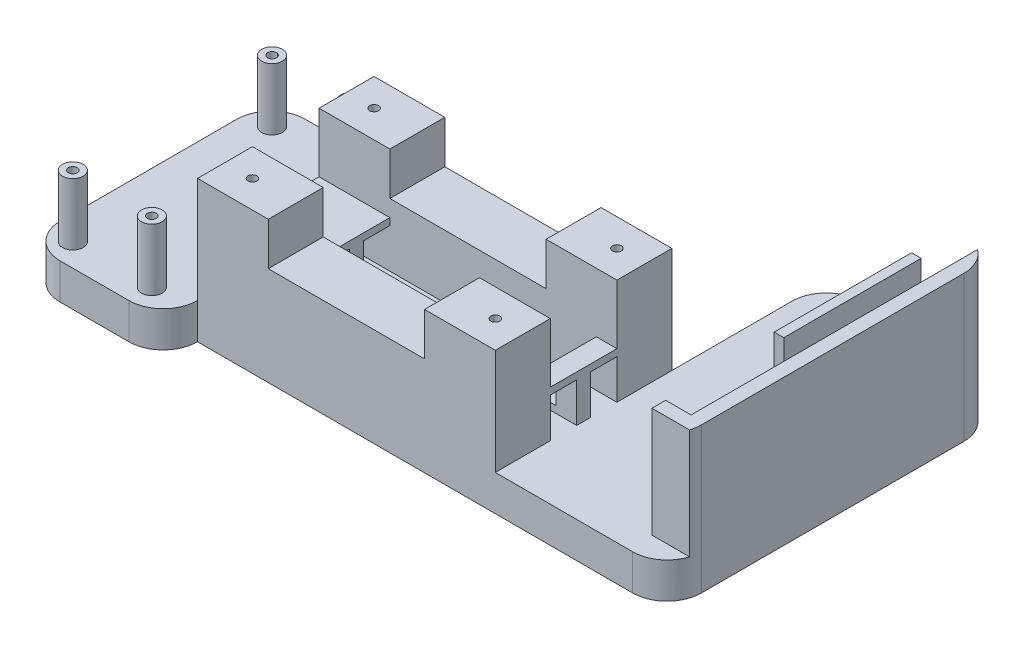
SolidWorks part; units mm, degrees
ref_plane "前视基准面" through (0, 0, 0) normal (0, 0, 1) x (1, 0, 0)
ref_plane "上视基准面" through (0, 0, 0) normal (0, 1, 0) x (1, 0, 0)
ref_plane "右视基准面" through (0, 0, 0) normal (1, 0, 0) x (0, 0, -1)
sketch "草图1" plane through (0, 0, 0) normal (0, 0, 1) x (1, 0, 0)
  line L1 (-42.1231, 25.5984) -> (44.5769, 25.5984)
  line L2 (-42.1231, 25.5984) -> (-42.1231, 5.5984)
  line L3 (-42.1231, 5.5984) -> (44.5769, 5.5984)
  line L4 (44.5769, 25.5984) -> (44.5769, 5.5984)
  line L5 (-21.5231, 25.5984) -> (23.9769, 25.5984)
  line L6 (-21.5231, 25.5984) -> (-21.5231, 13.1284)
  line L7 (-21.5231, 13.1284) -> (23.9769, 13.1284)
  line L8 (23.9769, 25.5984) -> (23.9769, 13.1284)
  dimension "D1" = 86.7
  dimension "D2" = 20
  dimension "D3" = 45.5
  dimension "D4" = 20.6
  dimension "D5" = 20.6
  dimension "D6" = 12.47
extrude "凸台-拉伸1" add sketch "草图1" along normal blind 16 contours L1 L8 L7 L6 L2 L3 L4 region at (-31.8231, 24.7086, 0)
sketch "草图2" plane through (0, 25.5984, 0) normal (0, 1, 0) x (1, 0, 0)
  line L0 (23.9769, -8) -> (28.5769, -8) construction
  line L1 (23.9769, -16) -> (23.9769, 0) construction
  line L2 (28.5769, -8) -> (28.5769, 0) construction
  line L3 (23.9769, 0) -> (44.5769, 0) construction
  line L4 (28.5769, 0) -> (28.5769, -16) construction
  line L5 (23.9769, -16) -> (44.5769, -16) construction
  line L7 (28.5769, 0) -> (44.5769, -16) construction
  line L8 (44.5769, 0) -> (28.5769, -16) construction
  point P16 (36.5769, -8)
  dimension "D1" = 4.6
hole_wizard "Ø1.0mm 暗销孔1" positions "草图2" profile "草图3" hole size "Ø1.0" standard "GB" end condition through all
sketch "草图3" plane through (36.5769, 25.5984, 8) normal (1, 0, 0) x (0, 0, 1)
  line L0 (0, 0) -> (0, 20)
  line L1 (0, 20) -> (1.3, 20)
  line L2 (1.3, 20) -> (1.3, 0)
  line L5 (1.3, 0) -> (0, 0)
  line L11 (0, -6.35) -> (0, 107.95) construction
  dimension "通孔孔直径" = 2.6
  dimension "通孔孔深度" = 20
sketch "草图4" plane through (0, 25.5984, 0) normal (0, 1, 0) x (1, 0, 0)
  line L0 (-21.5231, -8) -> (-26.1231, -8) construction
  line L1 (-21.5231, -16) -> (-21.5231, 0) construction
  line L2 (-26.1231, -8) -> (-26.1231, 0) construction
  line L3 (-42.1231, 0) -> (-21.5231, 0) construction
  line L4 (-26.1231, 0) -> (-26.1231, -16) construction
  line L5 (-42.1231, -16) -> (-21.5231, -16) construction
  line L6 (-42.1231, 0) -> (-26.1231, -16) construction
  line L7 (-26.1231, -16) -> (-26.1231, 0) construction
  line L8 (-26.1231, 0) -> (-42.1231, -16) construction
  point P15 (-34.1231, -8)
  dimension "D1" = 4.6
hole_wizard "Ø1.0mm 暗销孔2" positions "草图4" profile "草图5" hole size "Ø1.0" standard "GB" end condition through all
sketch "草图5" plane through (-34.1231, 25.5984, 8) normal (1, 0, 0) x (0, 0, 1)
  line L0 (0, 0) -> (0, 20)
  line L1 (0, 20) -> (1.3, 20)
  line L2 (1.3, 20) -> (1.3, 0)
  line L5 (1.3, 0) -> (0, 0)
  line L11 (0, -6.35) -> (0, 107.95) construction
  dimension "通孔孔直径" = 2.6
  dimension "通孔孔深度" = 20
sketch "草图7" plane through (0, 25.5984, 0) normal (0, 1, 0) x (1, 0, 0)
sketch "草图8" plane through (0, 5.5984, 0) normal (0, -1, 0) x (1, 0, 0)
  line L1 (-42.1231, 16) -> (44.5769, 16)
  line L2 (-42.1231, 16) -> (-42.1231, 0)
  line L3 (-42.1231, 0) -> (44.5769, 0)
  line L4 (44.5769, 16) -> (44.5769, 0)
extrude "凸台-拉伸2" add sketch "草图8" along normal blind 21.2
sketch "草图9" plane through (0, 0, 0) normal (0, 0, -1) x (-1, 0, 0)
  line L0 (42.1231, 25.5984) -> (42.1231, -15.6016) construction
  line L1 (-44.5769, -15.6016) -> (42.1231, -15.6016)
  line L2 (-44.5769, -15.6016) -> (-44.5769, -5.2016)
  line L3 (-44.5769, -5.2016) -> (42.1231, -5.2016)
  line L4 (42.1231, -15.6016) -> (42.1231, -5.2016)
  dimension "D1" = 10.4
extrude "凸台-拉伸3" add sketch "草图9" along normal blind 9.7
sketch "草图15" plane through (0, -5.2016, 0) normal (0, 1, 0) x (1, 0, 0)
  line L5 (-42.1231, 9.7) -> (-21.5231, 9.7)
  line L6 (-42.1231, 9.7) -> (-42.1231, 7.7)
  line L7 (-42.1231, 7.7) -> (-21.5231, 7.7)
  line L8 (-21.5231, 9.7) -> (-21.5231, 7.7)
  dimension "D1" = 2
extrude "凸台-拉伸8" add sketch "草图15" along normal blind 13.5
sketch "草图16" plane through (0, 0, -9.7) normal (0, 0, -1) x (-1, 0, 0)
  line L0 (42.1231, -15.6016) -> (42.1231, 8.2984) construction
  line L1 (21.5231, 8.2984) -> (42.1231, 8.2984)
  line L2 (21.5231, 8.2984) -> (21.5231, 6.2984)
  line L3 (21.5231, 6.2984) -> (42.1231, 6.2984)
  line L4 (42.1231, 8.2984) -> (42.1231, 6.2984)
  dimension "D1" = 2
extrude "凸台-拉伸9" add sketch "草图16" against normal blind 10.5
mirror "镜向20" about plane through (0, 0, -9.7) normal (0, 0, 1) of "Ø1.0mm 暗销孔2", "Ø1.0mm 暗销孔1", "凸台-拉伸3", "凸台-拉伸1", "凸台-拉伸2", "凸台-拉伸8", "凸台-拉伸9"
sketch "草图19" plane through (44.5769, 0, 0) normal (1, 0, 0) x (0, 0, -1)
  line L0 (35.4, 25.5984) -> (35.4, -15.6016) construction
  line L1 (-16, -15.6016) -> (35.4, -15.6016)
  line L2 (-16, -15.6016) -> (-16, -5.2016)
  line L3 (-16, -5.2016) -> (35.4, -5.2016)
  line L4 (35.4, -15.6016) -> (35.4, -5.2016)
  line L5 (19.4, -5.2016) -> (0, -5.2016) construction
  dimension "D1" = 0
  dimension "D2" = 10.4
extrude "凸台-拉伸10" add sketch "草图19" along normal blind 50
sketch "草图25" plane through (0, 0, -35.4) normal (0, 0, -1) x (-1, 0, 0)
  line L0 (-94.5769, -15.6016) -> (42.1231, -15.6016) construction
  line L1 (-94.5769, -5.2016) -> (-44.5769, -5.2016)
  line L2 (-94.5769, -5.2016) -> (-94.5769, -15.6016)
  line L3 (-94.5769, -15.6016) -> (-44.5769, -15.6016)
  line L4 (-44.5769, -5.2016) -> (-44.5769, -15.6016)
extrude "凸台-拉伸11" add sketch "草图25" along normal blind 45
sketch "草图26" plane through (0, -5.2016, 0) normal (0, 1, 0) x (1, 0, 0)
  line L0 (44.5769, 0) -> (94.5769, 0) construction
  line L1 (94.5769, 80.4) -> (94.5769, -16) construction
  line L2 (44.5769, 80.4) -> (94.5769, 80.4) construction
  line L7 (83.1769, -9) -> (94.5769, -9)
  line L8 (83.1769, -9) -> (83.1769, -5)
  line L9 (83.1769, -5) -> (90.5769, -5)
  line L10 (94.5769, -9) -> (94.5769, -5)
  line L12 (94.5769, -5) -> (94.5769, 80.4)
  line L13 (94.5769, 80.4) -> (90.5769, 80.4)
  line L14 (90.5769, -5) -> (90.5769, 80.4)
  line L15 (83.1769, -5) -> (83.1769, 28) construction
  line L29 (83.1769, 28) -> (84.5769, 28)
  line L31 (83.1769, 68) -> (84.5769, 68)
  line L32 (84.5769, 28) -> (84.5769, 68)
  line L36 (83.1769, 68) -> (83.1769, 83.3786) construction
  line L37 (83.1769, 28) -> (81.7769, 28)
  line L39 (83.1769, 68) -> (81.7769, 68)
  line L40 (81.7769, 28) -> (81.7769, 68)
  dimension "D1" = 4
  dimension "D2" = 5
  dimension "D3" = 4
  dimension "D4" = 7.4
  dimension "D5" = 1.4
  dimension "D6" = 28
  dimension "D7" = 1.4
  dimension "D8" = 40
  dimension "D9" = 6
extrude "凸台-拉伸12" add sketch "草图26" along normal blind 32
sketch "草图28" plane through (0, -5.2016, 0) normal (0, 1, 0) x (1, 0, 0)
  line L0 (84.5769, 28) -> (84.5769, 68) construction
  line L13 (90.5769, -5) -> (84.5769, -5)
  line L14 (90.5769, -5) -> (90.5769, 80.4)
  line L15 (90.5769, 80.4) -> (84.5769, 80.4)
  line L16 (84.5769, 28) -> (84.5769, 80.4)
  line L17 (94.5769, 80.4) -> (90.5769, 80.4) construction
  line L19 (84.5769, -5) -> (82.5769, -5)
  line L21 (84.5769, 28) -> (82.5769, 28)
  line L22 (82.5769, -5) -> (82.5769, 28)
  dimension "D1" = 6
  dimension "D2" = 0
  dimension "D3" = 2
  dimension "D4" = 33
extrude "切除-拉伸1" cut sketch "草图28" against normal blind 5
sketch "草图29" plane through (-42.1231, 0, 0) normal (-1, 0, 0) x (0, 0, 1)
  line L0 (-35.4, 25.5984) -> (-35.4, -15.6016) construction
  line L1 (-35.4, -5.1986) -> (16, -5.1986)
  line L2 (-35.4, -5.1986) -> (-35.4, -15.6016)
  line L3 (-35.4, -15.6016) -> (16, -15.6016)
  line L4 (16, -5.1986) -> (16, -15.6016)
extrude "凸台-拉伸13" add sketch "草图29" along normal blind 40
sketch "草图32" plane through (0, 0, -35.4) normal (0, 0, -1) x (-1, 0, 0)
  line L1 (42.1231, -5.1986) -> (82.1231, -5.1986)
  line L2 (42.1231, -5.1986) -> (42.1231, -15.6016)
  line L3 (42.1231, -15.6016) -> (82.1231, -15.6016)
  line L4 (82.1231, -5.1986) -> (82.1231, -15.6016)
extrude "凸台-拉伸14" add sketch "草图32" along normal blind 10
sketch "草图33" plane through (0, 0, 16) normal (0, 0, 1) x (1, 0, 0)
  line L0 (94.5769, -15.6016) -> (-82.1231, -15.6016) construction
  line L1 (-82.1231, -5.1986) -> (-42.1231, -5.1986)
  line L2 (-82.1231, -5.1986) -> (-82.1231, -15.6016)
  line L3 (-82.1231, -15.6016) -> (-42.1231, -15.6016)
  line L4 (-42.1231, -5.1986) -> (-42.1231, -15.6016)
extrude "凸台-拉伸15" add sketch "草图33" along normal blind 10
sketch "草图34" plane through (0, -5.1986, 0) normal (0, 1, 0) x (1, 0, 0)
  line L0 (-42.1231, 9.7) -> (-82.1231, 9.7) construction
  line L1 (-55.1231, 38.7) -> (-72.1231, 38.7)
  line L2 (-52.1231, 35.7) -> (-52.1231, -16.3)
  line L3 (-55.1231, -19.3) -> (-72.1231, -19.3)
  line L4 (-75.1231, 35.7) -> (-75.1231, -16.3)
  line L5 (-42.1231, 7.7) -> (-42.1231, 11.7) construction
  line L6 (-82.1231, -26) -> (-82.1231, 45.4) construction
  line L7 (-42.1231, 11.7) -> (-42.1231, 19.4) construction
  circle A0 centre (-52.1231, 38.7) radius 3
  circle A1 centre (-52.1231, -19.3) radius 3
  circle A2 centre (-75.1231, 38.7) radius 3
  circle A3 centre (-75.1231, -19.3) radius 3
  dimension "D4" = 6
  dimension "D5" = 6
  dimension "D7" = 6
  dimension "D8" = 6
  dimension "D1" = 23
  dimension "D2" = 58
  dimension "D3" = 29
  dimension "D6" = 10
extrude "凸台-拉伸16" add sketch "草图34" along normal blind 18 contours A0 | A2 | A1 | A3 region at (-52.1231, -5.1986, -38.7) region at (-75.1231, -5.1986, -38.7) region at (-52.1231, -5.1986, 19.3) region at (-75.1231, -5.1986, 19.3)
sketch "草图35" plane through (0, 12.8014, 0) normal (0, 1, 0) x (1, 0, 0)
  point P0 (-52.1231, 38.7)
hole_wizard "Ø1.0mm 暗销孔3" positions "草图35" profile "草图36" hole size "Ø1.0" standard "GB" end condition through all
sketch "草图36" plane through (-52.1231, 12.8014, -38.7) normal (1, 0, 0) x (0, 0, 1)
  line L0 (0, 0) -> (0, 28.403)
  line L1 (0, 28.403) -> (1.3, 28.403)
  line L2 (1.3, 28.403) -> (1.3, 0)
  line L5 (1.3, 0) -> (0, 0)
  line L11 (0, -6.35) -> (0, 107.95) construction
  dimension "通孔孔直径" = 2.6
  dimension "通孔孔深度" = 28.403
sketch "草图37" plane through (0, 12.8014, 0) normal (0, 1, 0) x (1, 0, 0)
  line L0 (-75.1231, 41.7) -> (-75.1231, 35.7) construction
  line L1 (-75.1231, 35.7) -> (-72.1231, 38.7) construction
  line L2 (-72.1231, 38.7) -> (-78.1231, 38.7) construction
  line L3 (-75.1231, -16.3) -> (-75.1231, -22.3) construction
  line L4 (-75.1231, -22.3) -> (-72.1231, -19.3) construction
  line L5 (-72.1231, -19.3) -> (-78.1231, -19.3) construction
  line L6 (-52.1231, -16.3) -> (-52.1231, -22.3) construction
  line L7 (-52.1231, -22.3) -> (-49.1231, -19.3) construction
  line L8 (-49.1231, -19.3) -> (-55.1231, -19.3) construction
  circle A0 centre (-75.1231, 38.7) radius 3 construction
  circle A1 centre (-75.1231, 38.7) radius 3 construction
  circle A2 centre (-75.1231, -19.3) radius 3 construction
  circle A3 centre (-75.1231, -19.3) radius 3 construction
  circle A4 centre (-52.1231, -19.3) radius 3 construction
  circle A5 centre (-52.1231, -19.3) radius 3 construction
  point P29 (-75.1231, 38.7)
  point P31 (-75.1231, -19.3)
  point P33 (-52.1231, -19.3)
hole_wizard "Ø1.0mm 暗销孔4" positions "草图37" profile "草图38" hole size "Ø1.0" standard "GB" end condition through all
sketch "草图38" plane through (-52.1231, 12.8014, 19.3) normal (1, 0, 0) x (0, 0, 1)
  line L0 (0, 0) -> (0, 28.403)
  line L1 (0, 28.403) -> (1.3, 28.403)
  line L2 (1.3, 28.403) -> (1.3, 0)
  line L5 (1.3, 0) -> (0, 0)
  line L11 (0, -6.35) -> (0, 107.95) construction
  dimension "通孔孔直径" = 2.6
  dimension "通孔孔深度" = 28.403
sketch "草图39" plane through (0, -5.1986, 0) normal (0, 1, 0) x (1, 0, 0)
  line L0 (-75.1231, 38.7) -> (-52.1231, 38.7) construction
  line L1 (-52.1231, 38.7) -> (-52.1231, -19.3) construction
fillet "圆角1" radius 10 6 edges at (44.5769, -10.4016, -80.4) (94.5769, -10.4016, 16) (-42.1231, -10.4001, -45.4) (-42.1231, -10.4001, 26) (-82.1231, -10.4001, -45.4) (-82.1231, -10.4001, 26)
fillet "圆角2" radius 10 1 edges at (94.5769, 5.5984, -80.4)
sketch "草图40" plane through (0, -5.2016, 0) normal (0, 1, 0) x (1, 0, 0)
  line L0 (23.9769, 19.4) -> (23.9769, 0) construction
  line L1 (44.5769, 19.4) -> (44.5769, 0) construction
  line L2 (23.9769, 9.7) -> (44.5769, 9.7) construction
  line L4 (38.5769, 11.7) -> (44.5769, 11.7)
  line L5 (38.5769, 11.7) -> (38.5769, 7.7)
  line L6 (38.5769, 7.7) -> (44.5769, 7.7)
  line L7 (44.5769, 11.7) -> (44.5769, 7.7)
  dimension "D1" = 6
  dimension "D2" = 4
  dimension "D3" = 2
extrude "凸台-拉伸17" add sketch "草图40" along normal blind 11.5
sketch "草图42" plane through (0, 6.2984, 0) normal (0, 1, 0) x (1, 0, 0)
  line L0 (38.5769, 9.7) -> (44.5769, 9.7) construction
  line L1 (38.5769, 11.7) -> (38.5769, 7.7) construction
  line L2 (44.5769, 7.7) -> (44.5769, 11.7) construction
  line L3 (41.5769, 11.7) -> (41.5769, 7.7) construction
  line L4 (44.5769, 11.7) -> (38.5769, 11.7) construction
  line L5 (38.5769, 7.7) -> (44.5769, 7.7) construction
  line L7 (38.5769, 0) -> (44.5769, 0)
  line L8 (38.5769, 0) -> (38.5769, 19.4)
  line L9 (38.5769, 19.4) -> (44.5769, 19.4)
  line L10 (44.5769, 0) -> (44.5769, 19.4)
  line L11 (38.5769, 0) -> (44.5769, 19.4) construction
  line L12 (38.5769, 19.4) -> (44.5769, 0) construction
  point P12 (41.5769, 9.7)
  dimension "D1" = 19.4
extrude "凸台-拉伸18" add sketch "草图42" along normal blind 2
sketch "草图44" plane through (0, -5.2016, 0) normal (0, 1, 0) x (1, 0, 0)
  line L0 (-21.5231, 11.7) -> (38.5769, 11.7) construction
  line L1 (-21.5231, 7.7) -> (38.5769, 7.7) construction
  line L2 (-21.5231, 7.7) -> (-21.5231, 11.7) construction
sketch "草图45" plane through (-42.1231, 0, 0) normal (-1, 0, 0) x (0, 0, 1)
  line L0 (-38.7, -5.1986) -> (19.3, -5.1986) construction
  line L1 (-11.7, 6.2984) -> (-7.7, 6.2984)
  line L2 (-11.7, 6.2984) -> (-11.7, -5.1986)
  line L3 (-11.7, -5.1986) -> (-7.7, -5.1986)
  line L4 (-7.7, 6.2984) -> (-7.7, -5.1986)
  line L5 (-7.7, 6.2984) -> (-7.7, -5.1986) construction
sketch "草图46" plane through (0, -5.2016, 0) normal (0, 1, 0) x (1, 0, 0)
  line L1 (-21.5231, 11.7) -> (38.5769, 11.7)
  line L2 (-21.5231, 11.7) -> (-21.5231, 7.7)
  line L3 (-21.5231, 7.7) -> (38.5769, 7.7)
  line L4 (38.5769, 11.7) -> (38.5769, 7.7)
extrude "凸台-拉伸19" add sketch "草图46" along normal blind 2
